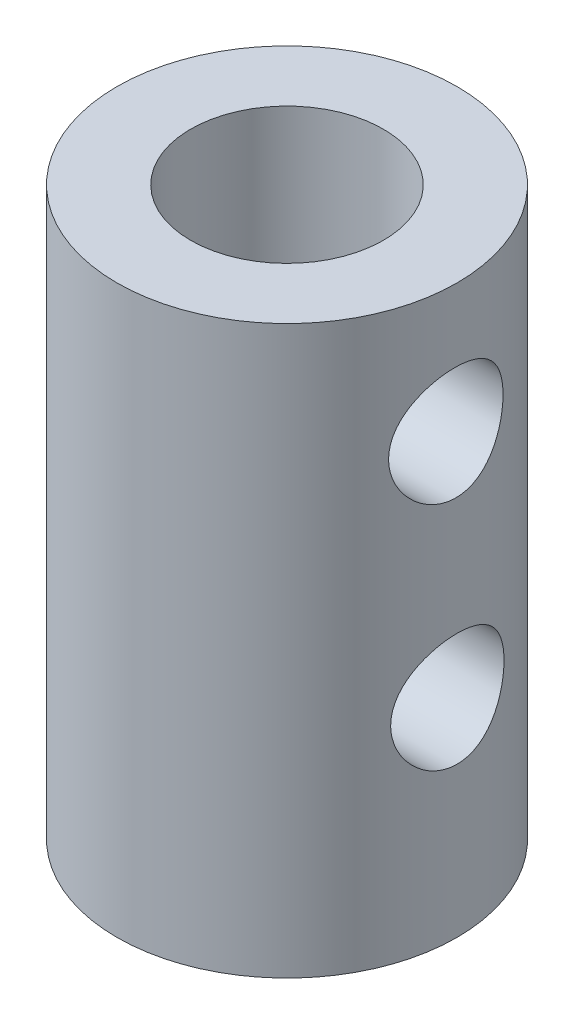
SolidWorks part; units mm, degrees
ref_plane "Front Plane" through (0, 0, 0) normal (0, 0, 1) x (1, 0, 0)
ref_plane "Top Plane" through (0, 0, 0) normal (0, 1, 0) x (1, 0, 0)
ref_plane "Right Plane" through (0, 0, 0) normal (1, 0, 0) x (0, 0, -1)
sketch "Sketch1" plane through (0, 0, 0) normal (0, 1, 0) x (1, 0, 0)
  circle A0 centre (0, 0) radius 6
extrude "Boss-Extrude1" add sketch "Sketch1" along normal blind 20
sketch "Sketch2" plane through (0, 20, 0) normal (0, 1, 0) x (1, 0, 0)
  circle A0 centre (0, 0) radius 3.4
extrude "Cut-Extrude1" cut sketch "Sketch2" against normal blind 13.55 contours A0
ref_plane "Plane1" through (0, 18.26, 0) normal (0, 1, 0) x (1, 0, 0)
ref_axis "Axis1" through (0, 6.45, 0) along (0, 1, 0)
ref_point "Point2"
sketch "Sketch5" plane through (0, 18.26, 0) normal (0, 1, 0) x (1, 0, 0)
  line L0 (0, 0) -> (2.6, 0) construction
  line L2 (2.6, -3.5716) -> (4.1507, -3.5716)
  line L3 (2.6, -3.5716) -> (2.6, 3.6126)
  line L4 (2.6, 3.6126) -> (4.1507, 3.6126)
  line L5 (4.1507, -3.5716) -> (4.1507, 3.6126)
extrude "Boss-Extrude2" add sketch "Sketch5" against normal blind 13.55
sketch "Sketch6" plane through (2.6, 0, 0) normal (-1, 0, 0) x (0, 0, 1)
  line L0 (-2.1909, 7.2921) -> (2.1909, 7.2921) construction
  line L1 (-2.1909, 6.45) -> (-2.1909, 18.26) construction
  line L2 (2.1909, 18.26) -> (2.1909, 6.45) construction
  line L3 (-2.1909, 15.4522) -> (2.1909, 15.4522) construction
  circle A0 centre (0.0542, 15.4522) radius 2
  circle A1 centre (0, 7.2921) radius 2
extrude "Cut-Extrude2" cut sketch "Sketch6" against normal blind 13.55
